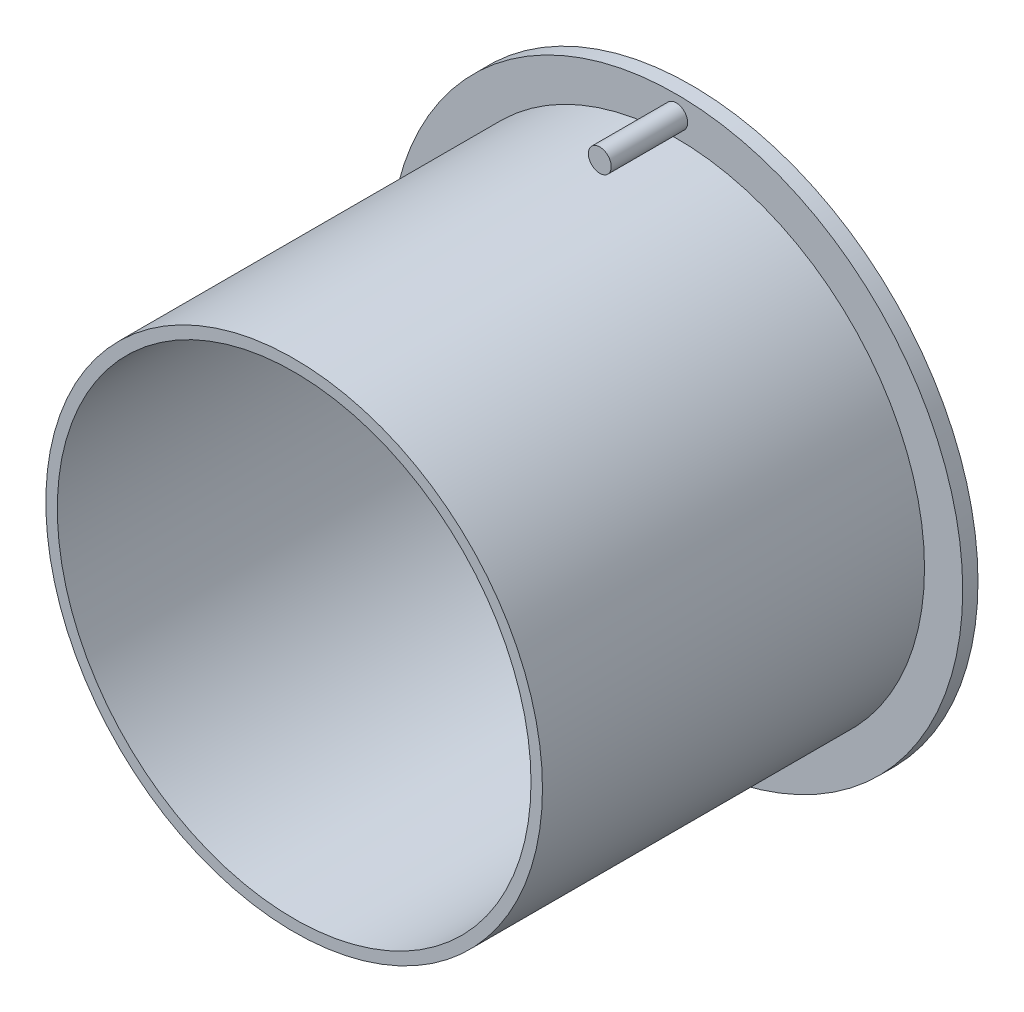
SolidWorks part; units mm, degrees
ref_plane "Front Plane" through (0, 0, 0) normal (0, 0, 1) x (1, 0, 0)
ref_plane "Top Plane" through (0, 0, 0) normal (0, 1, 0) x (1, 0, 0)
ref_plane "Right Plane" through (0, 0, 0) normal (1, 0, 0) x (0, 0, -1)
sketch "Sketch1" plane through (0, 0, 0) normal (0, 0, 1) x (1, 0, 0)
  circle A0 centre (0, 0) radius 37.5
  circle A1 centre (0, 0) radius 32.5
  circle A2 centre (0, 0) radius 31
  dimension "D1" = 75
  dimension "D2" = 65
  dimension "D3" = 62
extrude "Boss-Extrude1" add sketch "Sketch1" against normal blind 2 contours A0 A1 | A1 A2 | A2 region at (-36.4393, 0, 0) region at (-31.5808, 0, 0) region at (0, 0, 0)
sketch "Sketch2" plane through (0, 0, 0) normal (0, 0, 1) x (1, 0, 0)
  circle A0 centre (0, 0) radius 32.5
  circle A1 centre (0, 0) radius 31
  dimension "D1" = 65
  dimension "D2" = 62
extrude "Boss-Extrude2" add sketch "Sketch2" along normal blind 55
sketch "Sketch3" plane through (0, 0, -2) normal (0, 0, -1) x (-1, 0, 0)
  line L0 (0, 37.5) -> (0, 32.5)
  line L1 (0, -32.5) -> (0, -37.5)
  line L2 (0, 37.5) -> (0, 35)
  line L3 (0, 35) -> (6.0304, 35)
  line L4 (0, -35) -> (6.0304, -35)
  circle A0 centre (0, 0) radius 32.5
  circle A3 centre (0, 0) radius 37.5 construction
  dimension "D1" = 65
sketch "Sketch8" plane through (0, 0, 0) normal (0, 0, 1) x (1, 0, 0)
  circle A2 centre (0, 35) radius 1.5
  circle A3 centre (0, -35) radius 1.5
  dimension "D1" = 3
  dimension "D2" = 3
extrude "Boss-Extrude3" add sketch "Sketch8" along normal blind 10
sketch "Sketch9" plane through (0, 0, 55) normal (0, 0, 1) x (1, 0, 0)
  circle A0 centre (0, 0) radius 32.5
  circle A1 centre (0, 0) radius 31
extrude "Cut-Extrude1" cut sketch "Sketch9" against normal blind 5
